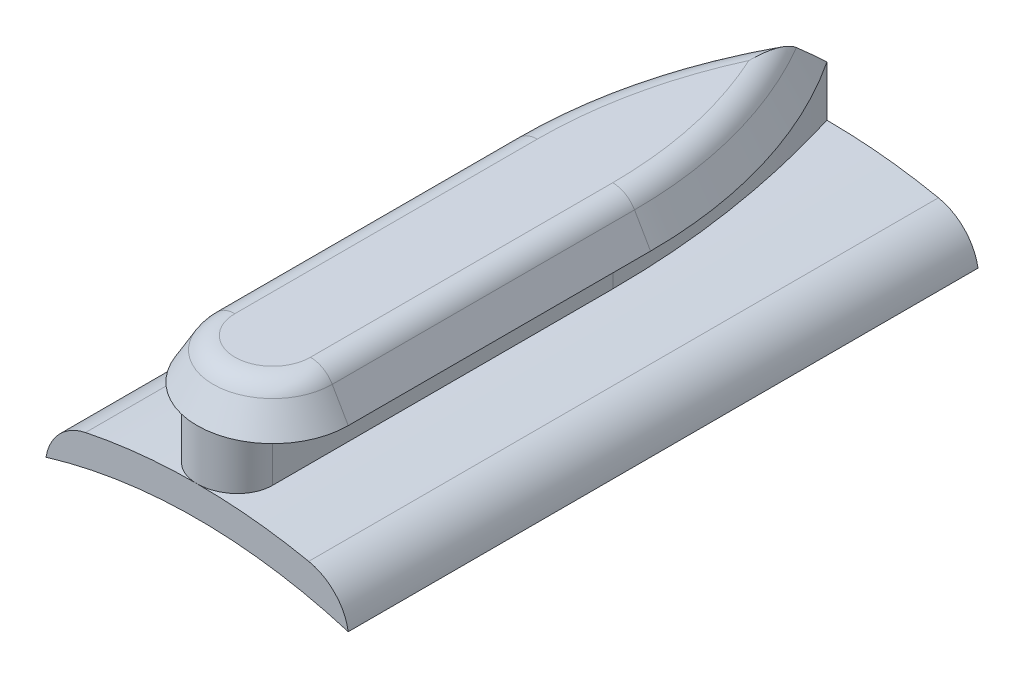
SolidWorks part; units mm, degrees
material "PLA"
ref_plane "Front Plane" through (0, 0, 0) normal (0, 0, 1) x (1, 0, 0)
ref_plane "Top Plane" through (0, 0, 0) normal (0, 1, 0) x (1, 0, 0)
ref_plane "Right Plane" through (0, 0, 0) normal (1, 0, 0) x (0, 0, -1)
sketch "Sketch1" plane through (0, 0, 0) normal (0, 0, 1) x (1, 0, 0)
  line L0 (0, 0.4773) -> (0, 0.8662) construction
  arc A0 (12, -1.7728) -> (-12, -1.7728) centre (0, -41.5) ccw
  arc A1 (8.8602, 1.4966) -> (-8.8602, 1.4966) centre (0, -41.5) ccw
  arc A2 (8.8602, 1.4966) -> (12, -1.7728) centre (8.0529, -2.4211) cw
  arc A3 (-12, -1.7728) -> (-8.8602, 1.4966) centre (-8.0529, -2.4211) cw
  point P12 (8.0247, 1.6603)
  dimension "D1" = 2.4
  dimension "D2" = 83
  dimension "D4" = 4
  dimension "D3" = 24
extrude "Boss-Extrude1" add sketch "Sketch1" along normal blind 50
ref_plane "Plane1" through (0, 2.4, 0) normal (0, 1, 0) x (1, 0, 0)
sketch "Sketch2" plane through (0, 2.4, 0) normal (0, 1, 0) x (1, 0, 0)
  line L0 (-3, -20) -> (-3, -47)
  line L1 (3, -47) -> (3, -20)
  line L2 (0, -1.7439) -> (0, -17.5068) construction
  line L3 (-8.8602, -50) -> (8.8602, -50) construction
  line L4 (8.8602, 0) -> (-8.8602, 0) construction
  arc A0 (-3, -47) -> (3, -47) centre (0, -47) ccw
  arc A1 (3, -20) -> (0, 0) centre (-65.1667, -20) ccw
  arc A2 (-3, -20) -> (0, 0) centre (65.1667, -20) cw
  point P15 (3, -25.9208)
  point P16 (3, -14.9755)
  dimension "D1" = 6
  dimension "D2" = 20
extrude "Boss-Extrude2" add sketch "Sketch2" along normal blind 4 and the other way up to surface other way up to face at (0, 1.9483, 25)
sketch "Sketch3" plane through (0, 6.4, 0) normal (0, 1, 0) x (1, 0, 0)
  line L0 (0, 14.8835) -> (0, -27.446) construction
  line L1 (-6, -20) -> (-6, -44)
  line L2 (6, -44) -> (6, -20)
  arc A0 (-6, -44) -> (6, -44) centre (0, -44) ccw
  arc A1 (6, -20) -> (0, 0) centre (-30.3333, -20) ccw
  arc A2 (-6, -20) -> (0, 0) centre (30.3333, -20) cw
  arc A4 (-3, -47) -> (3, -47) centre (0, -47) ccw construction
  point P14 (0, 0)
  point P16 (5, -26.2812)
  point P17 (0, 0)
  dimension "D2" = 20
  dimension "D1" = 12
extrude "Boss-Extrude3" add sketch "Sketch3" along normal blind 3.2 draft 30
fillet "Fillet1" radius 2 5 edges at (-3.0982, 9.6, 11.5383) (-4.1525, 9.6, 32) (3.0982, 9.6, 11.5383) (4.1525, 9.6, 32) (0, 9.6, 48.1525)
sketch "Sketch4" plane through (0, 0, 0) normal (0, 1, 0) x (1, 0, 0)
  line L0 (-4, -50) -> (-4, 0) construction
  line L1 (12, 0) -> (-12, 0) construction
  line L2 (-12, -50) -> (12, -50) construction
  text T0 "← UP ←" font "Century Gothic" height 8
  point P4 (-3.4942, -50)
  point P8 (0, 0)
  point P10 (-8.2238, -7.8817)
  dimension "D1" = 4
extrude "Cut-Extrude1" cut sketch "Sketch4" along normal blind 0.2 and the other way through all
